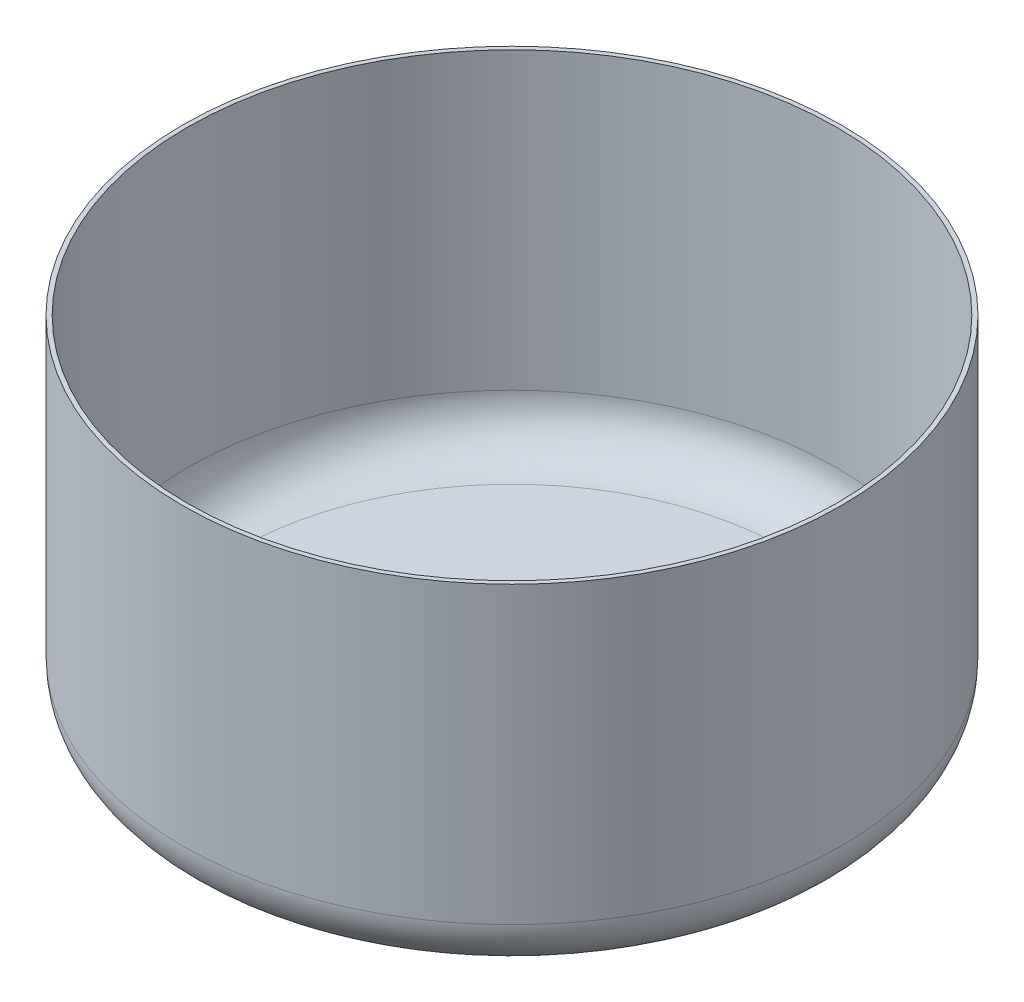
SolidWorks part; units mm, degrees
material "Rubber"
ref_plane "Front" through (0, 0, 0) normal (0, 0, 1) x (1, 0, 0)
ref_plane "Top" through (0, 0, 0) normal (0, 1, 0) x (1, 0, 0)
ref_plane "Right" through (0, 0, 0) normal (1, 0, 0) x (0, 0, -1)
sketch "Sketch1" plane through (0, 0, 0) normal (0, 1, 0) x (1, 0, 0)
  circle A0 centre (0, 0) radius 482.6
  dimension "D1" = 965.2
extrude "Boss-Extrude1" add sketch "Sketch1" along normal blind 508
fillet "Fillet1" radius 76.2 1 edges at (0, 0, 482.6)
shell "Shell1" thickness 6.35 removed face at (0, 508, 482.6)
sketch "Sketch2" plane through (0, 0, 0) normal (0, 0, 1) x (1, 0, 0)
  line L0 (0, 0) -> (0, 4013.2)
  line L1 (0, 4013.2) -> (1016, 4013.2)
  line L2 (1016, 4013.2) -> (304.8, 3172.7744)
  line L3 (304.8, 3172.7744) -> (1016, 3172.7744)
  line L4 (1016, 3172.7744) -> (304.8, 2332.3488)
  line L5 (304.8, 2332.3488) -> (1016, 2332.3488)
  line L6 (1016, 2332.3488) -> (304.8, 1491.9232)
  line L7 (304.8, 1491.9232) -> (76.2, 1491.9232)
  line L8 (76.2, 1491.9232) -> (76.2, 508)
  line L9 (482.6, 508) -> (-482.6, 508) construction
  line L10 (476.25, 508) -> (-476.25, 508) construction
  line L11 (1016, 4013.2) -> (1016, 3172.7744) construction
  line L12 (1016, 3172.7744) -> (1016, 2332.3488) construction
  line L13 (1016, 2332.3488) -> (1016, 1491.9232) construction
  line L14 (1016, 1491.9232) -> (304.8, 1491.9232) construction
  line L15 (0, 4013.2) -> (-1016, 4013.2) construction
  line L16 (76.2, 1491.9232) -> (0, 1491.9232) construction
  line L17 (0, 1491.9232) -> (-76.2, 1491.9232) construction
  line L18 (76.2, 508) -> (76.2, 0)
  line L19 (-406.4, 0) -> (406.4, 0) construction
  line L20 (76.2, 0) -> (0, 0)
  dimension "D1" = 3505.2
  dimension "D2" = 2032
  dimension "D3" = 304.8
  dimension "D4" = 2521.2768
  dimension "D5" = 152.4
revolve "Revolve1" [suppressed] add sketch "Sketch2" angle 360 about L0
sketch "Sketch3" [suppressed] plane through (0, 4013.2, 0) normal (0, 1, 0) x (1, 0, 0)
  line L0 (0, 0) -> (0, -1016) construction
  line L1 (0, 0) -> (-508, -879.8818) construction
  line L2 (-63.5, -109.9852) -> (-508, -879.8818)
  line L3 (0, -127) -> (0, -1016)
  circle A0 centre (0, 0) radius 1016 construction
  arc A1 (-63.5, -109.9852) -> (0, -127) centre (0, 0) ccw
  arc A2 (-508, -879.8818) -> (0, -1016) centre (0, 0) ccw
  dimension "D1" = 254
  dimension "D2" = 30
extrude "Cut-Extrude1" [suppressed] cut sketch "Sketch3" against normal blind 3305.81
pattern_circular "CirPattern4" [suppressed] count 6 over 360 of bodies 181
